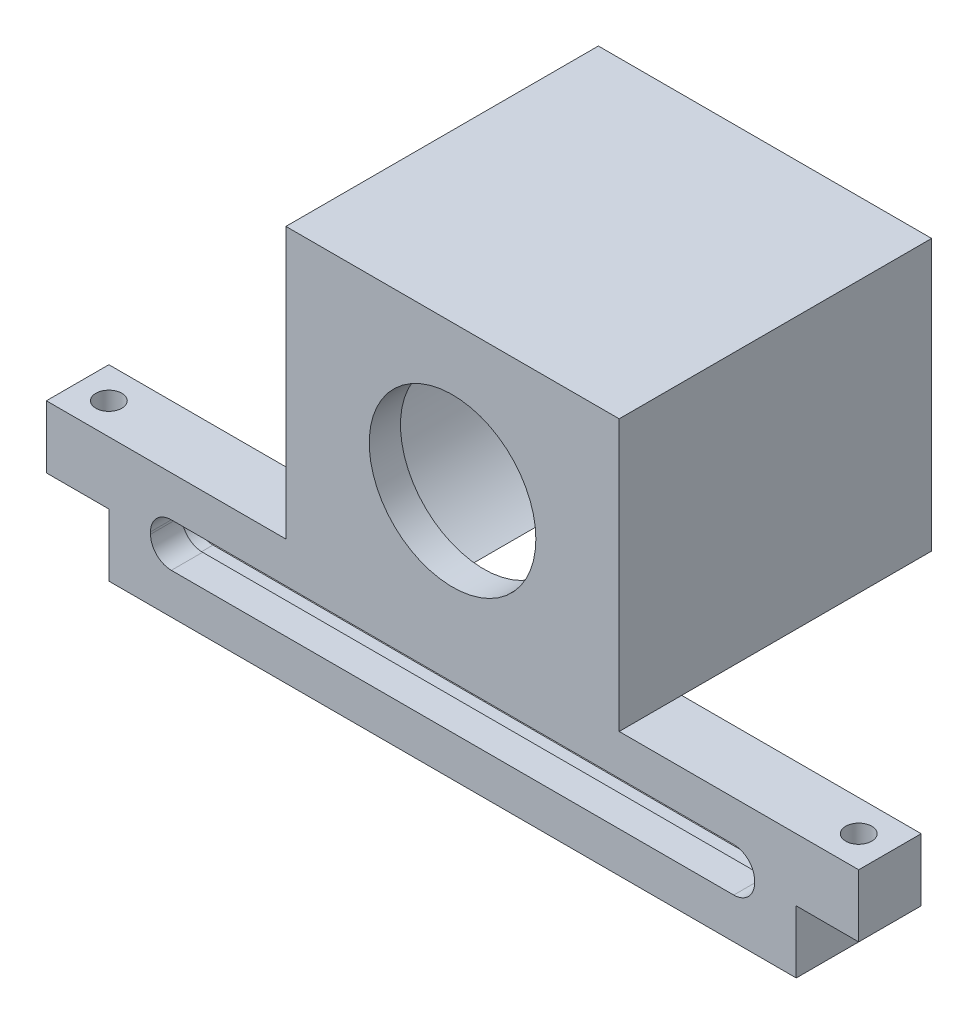
SolidWorks part; units mm, degrees
material "1060 Alloy"
ref_plane "Front Plane" through (0, 0, 0) normal (0, 0, 1) x (1, 0, 0)
ref_plane "Top Plane" through (0, 0, 0) normal (0, 1, 0) x (1, 0, 0)
ref_plane "Right Plane" through (0, 0, 0) normal (1, 0, 0) x (0, 0, -1)
sketch "Sketch1" plane through (0, 0, 0) normal (0, 0, 1) x (1, 0, 0)
  line L0 (0, 0) -> (6, 0)
  line L1 (6, 0) -> (6, -6)
  line L2 (6, -6) -> (72, -6)
  line L3 (72, -6) -> (72, 0)
  line L4 (72, 0) -> (78, 0)
  line L5 (78, 0) -> (78, 6)
  line L6 (78, 6) -> (55, 6)
  line L7 (55, 6) -> (55, 32)
  line L8 (55, 32) -> (23, 32)
  line L9 (23, 32) -> (23, 6)
  line L10 (23, 6) -> (0, 6)
  line L11 (0, 6) -> (0, 0)
  line L13 (10, 2.1) -> (68, 2.1)
  line L14 (10, 2.1) -> (10, -2.1)
  line L15 (10, -2.1) -> (68, -2.1)
  line L16 (68, 2.1) -> (68, -2.1)
  circle A0 centre (39, 18) radius 8
  dimension "D12" = 16
  dimension "D1" = 4.2
  dimension "D2" = 32
  dimension "D3" = 32
  dimension "D4" = 3.9
  dimension "D5" = 6
  dimension "D6" = 3.9
  dimension "D7" = 6
  dimension "D8" = 4
  dimension "D9" = 4
  dimension "D10" = 58
  dimension "D11" = 18
  dimension "D13" = 16
extrude "Boss-Extrude1" add sketch "Sketch1" along normal blind 30
sketch "Sketch3" plane through (0, 0, 0) normal (0, 0, -1) x (-1, 0, 0)
  circle A0 centre (-39, 18) radius 13
  dimension "D1" = 26
extrude "Cut-Extrude2" cut sketch "Sketch3" against normal offset from surface (27 mm away) 3 up to face at (39, 0, 30)
hole_wizard "Tap Drill for M3 Tap1" positions "Sketch5" profile "Sketch4" hole size "M3" standard "ISO"
sketch "Sketch5" plane through (53.9899, 0, -7.4052) normal (0, -1, 0) x (-1, 0, 0)
  line L4 (-24.0101, -37.4052) -> (-24.0101, -7.4052) construction
  line L5 (53.9899, -37.4052) -> (53.9899, -7.4052) construction
  line L7 (-18.0101, -37.4052) -> (-24.0101, -37.4052) construction
  point P0 (50.9899, -34.4052)
  point P2 (-21.0101, -34.4052)
  dimension "D1" = 3
  dimension "D2" = 3
  dimension "D3" = 3
sketch "Sketch4" plane through (3, 0, 27) normal (1, 0, 0) x (0, 0, -1)
  line L0 (0, 0) -> (0, 8.7511)
  line L1 (0, 8.7511) -> (1.25, 8)
  line L2 (1.25, 8) -> (1.25, 0)
  line L5 (1.25, 0) -> (0, 0)
  line L10 (0, 8.7511) -> (-1.25, 8) construction
  line L11 (0, -6.35) -> (0, 107.95) construction
  dimension "Hole Dia." = 2.5
  dimension "Hole Depth" = 8
  dimension "Drill Angle" = 118
sketch "Sketch6" plane through (0, 0, 0) normal (0, 0, -1) x (-1, 0, 0)
  line L2 (-78, 6) -> (0, 6)
  line L3 (-78, 6) -> (-78, -6)
  line L4 (-78, -6) -> (0, -6)
  line L5 (0, 6) -> (0, -6)
extrude "Cut-Extrude3" cut sketch "Sketch6" against normal offset from surface (24 mm away) 6 up to face at (39, 0, 30)
sketch "Sketch7" plane through (0, 0, 24) normal (0, 0, -1) x (-1, 0, 0)
  line L0 (-68, 2.1) -> (-68, -2.1) construction
  line L1 (-70, 4) -> (-8, 4)
  line L2 (-70, 4) -> (-70, -4)
  line L3 (-70, -4) -> (-8, -4)
  line L4 (-8, 4) -> (-8, -4)
  line L7 (-10, -2.1) -> (-10, 2.1) construction
  line L8 (-68, 2.1) -> (-10, 2.1) construction
  dimension "D1" = 2
  dimension "D2" = 8
  dimension "D3" = 1.9
  dimension "D4" = 2
extrude "Cut-Extrude4" cut sketch "Sketch7" against normal blind 3
fillet "Fillet1" radius 2 8 edges at (8, -4, 25.5) (10, -2.1, 28.5) (8, 4, 25.5) (10, 2.1, 28.5) (70, -4, 25.5) (68, -2.1, 28.5) (70, 4, 25.5) (68, 2.1, 28.5)
